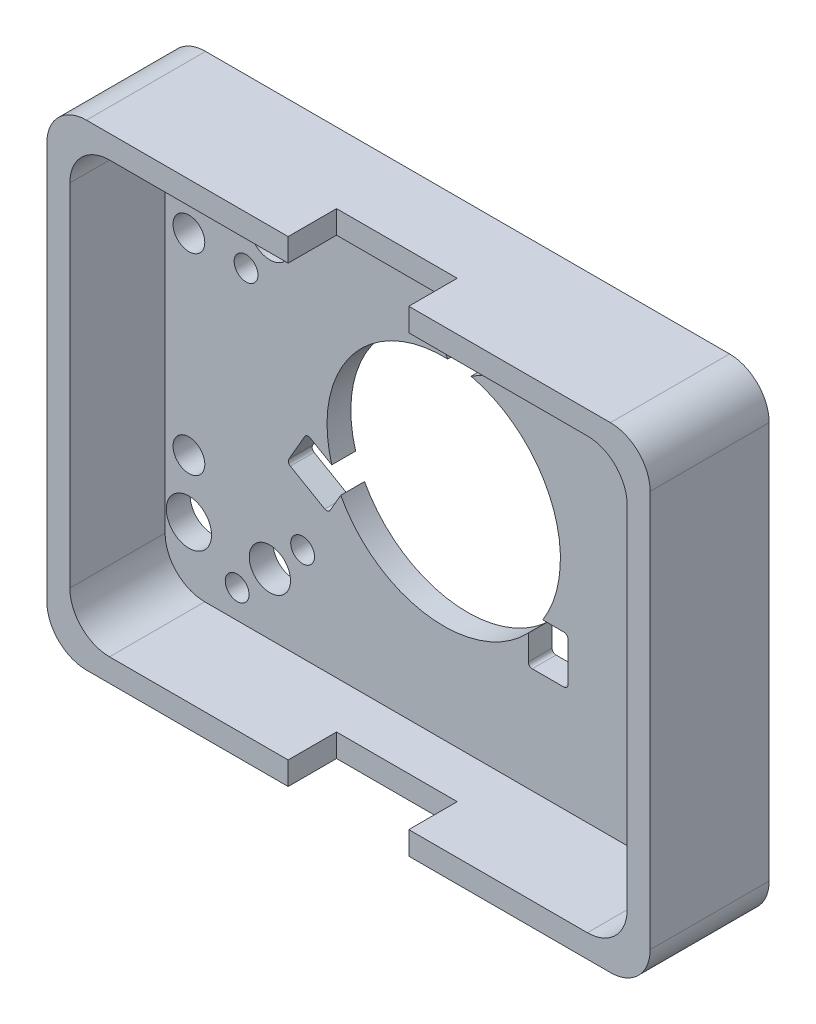
SolidWorks part; units mm, degrees
ref_plane "前基準面" through (0, 0, 0) normal (0, 0, 1) x (1, 0, 0)
ref_plane "上基準面" through (0, 0, 0) normal (0, 1, 0) x (1, 0, 0)
ref_plane "右基準面" through (0, 0, 0) normal (1, 0, 0) x (0, 0, -1)
sketch "草圖1" plane through (0, 0, 0) normal (0, 0, 1) x (1, 0, 0)
  line L1 (-33, 30) -> (33, 30)
  line L2 (-38, 25) -> (-38, -25)
  line L3 (-33, -30) -> (33, -30)
  line L4 (38, 25) -> (38, -25)
  line L5 (-38, 30) -> (38, -30) construction
  line L6 (-38, -30) -> (38, 30) construction
  arc A0 (-38, -25) -> (-33, -30) centre (-33, -25) ccw
  arc A1 (33, -30) -> (38, -25) centre (33, -25) ccw
  arc A2 (33, 30) -> (38, 25) centre (33, 25) cw
  arc A3 (-33, 30) -> (-38, 25) centre (-33, 25) ccw
  point P0 (0, 0)
  dimension "D3" = 5
  dimension "D1" = 76
  dimension "D2" = 60
extrude "填料-伸長1" add sketch "草圖1" along normal blind 15
sketch "草圖2" plane through (0, 0, 15) normal (0, 0, 1) x (1, 0, 0)
  line L0 (33, 30) -> (-33, 30) construction
  line L1 (-30.1, 27.1) -> (30.1, 27.1)
  line L2 (-35.1, 22.1) -> (-35.1, -22.1)
  line L3 (-30.1, -27.1) -> (30.1, -27.1)
  line L4 (35.1, 22.1) -> (35.1, -22.1)
  line L5 (-35.1, 27.1) -> (35.1, -27.1) construction
  line L6 (-35.1, -27.1) -> (35.1, 27.1) construction
  line L8 (-38, 25) -> (-38, -25) construction
  arc A0 (-35.1, -22.1) -> (-30.1, -27.1) centre (-30.1, -22.1) ccw
  arc A1 (30.1, -27.1) -> (35.1, -22.1) centre (30.1, -22.1) ccw
  arc A2 (30.1, 27.1) -> (35.1, 22.1) centre (30.1, 22.1) cw
  arc A3 (-30.1, 27.1) -> (-35.1, 22.1) centre (-30.1, 22.1) ccw
  point P0 (0, 0)
  dimension "D3" = 5
  dimension "D1" = 2.9
  dimension "D2" = 2.9
extrude "除料-伸長1" cut sketch "草圖2" against normal blind 12
sketch "草圖3" plane through (0, 0, 0) normal (0, 1, 0) x (1, 0, 0)
  line L0 (0, 11.6056) -> (0, -27.4941) construction
  line L1 (0, -3) -> (14.7, -3)
  line L2 (30.1, -3) -> (-30.1, -3) construction
  line L3 (14.7, -3) -> (14.7, -1.9)
  line L6 (0, -1.9) -> (0, -3)
  line L7 (14.7, -1.9) -> (14.7, 0)
  line L8 (33, 0) -> (-33, 0) construction
  line L9 (14.7, 0) -> (0, 0)
  line L10 (0, 0) -> (0, -1.9)
  dimension "D1" = 14.7
  dimension "D2" = 14.7
  dimension "D3" = 1.1
revolve "除料-旋轉1" cut sketch "草圖3" angle 360 about L0
ref_plane "平面1" through (0, 0, 15) normal (0, 0, 1) x (1, 0, 0)
sketch "草圖4" plane through (0, 0, 15) normal (0, 0, 1) x (1, 0, 0)
  line L0 (0, 32.9941) -> (0, -32.6269) construction
  line L1 (-42.1259, 0) -> (41.8506, 0) construction
  line L2 (7.6, 30) -> (-7.6, 30)
  line L3 (33, 30) -> (-33, 30) construction
  line L4 (-7.6, 30) -> (-7.6, 27.1)
  line L5 (30.1, 27.1) -> (-30.1, 27.1) construction
  line L6 (-7.6, 27.1) -> (7.6, 27.1)
  line L7 (30.1, 27.1) -> (-30.1, 27.1) construction
  line L8 (0, 27.1) -> (0, 30)
  line L9 (7.6, 30) -> (7.6, 27.1)
  line L10 (-7.6, -30) -> (-7.6, -27.1)
  line L11 (7.6, -30) -> (-7.6, -30)
  line L12 (7.6, -30) -> (7.6, -27.1)
  line L13 (-7.6, -27.1) -> (7.6, -27.1)
  dimension "D1" = 7.6
extrude "除料-伸長2" cut sketch "草圖4" against normal blind 6.1 contours L6 L9 L2 L4 | L11 L10 L13 L12
sketch "草圖5" plane through (0, 0, 3) normal (0, 0, 1) x (1, 0, 0)
  line L0 (0, 27.1) -> (0, -27.1) construction
  line L1 (30.1, 27.1) -> (-30.1, 27.1) construction
  line L2 (-7.6, -27.1) -> (7.6, -27.1) construction
  line L3 (-35.1, 0) -> (35.1, 0) construction
  line L4 (-35.1, 22.1) -> (-35.1, -22.1) construction
  line L5 (35.1, -22.1) -> (35.1, 22.1) construction
  line L6 (-35.1, 22.1) -> (-25.1, 22.1) construction
  line L7 (-25.1, 22.1) -> (-25.1, -22.1) construction
  line L8 (-25.1, -22.1) -> (-35.1, -22.1) construction
  line L9 (-35.1, 22.1) -> (-35.1, -22.1) construction
  line L10 (35.1, -22.1) -> (35.1, 22.1) construction
  line L11 (13.15, 0) -> (13.15, -16.56) construction
  line L12 (11.15, -8.28) -> (15.15, -8.28) construction
  line L13 (11.15, -7.78) -> (15.15, -7.78) construction
  line L14 (15.15, -7.78) -> (15.15, -8.78) construction
  line L15 (15.15, -8.78) -> (11.15, -8.78) construction
  line L16 (11.15, -8.78) -> (11.15, -7.78) construction
  line L17 (0, 0) -> (-14.4458, 25.0209) construction
  line L18 (-6.575, 11.3882) -> (6.9004, 19.1682) construction
  line L19 (-0.8373, 17.0103) -> (1.1627, 13.5462) construction
  line L20 (-0.8373, 17.0103) -> (0.0287, 17.5103) construction
  line L21 (0.0287, 17.5103) -> (2.0287, 14.0462) construction
  line L22 (2.0287, 14.0462) -> (1.1627, 13.5462) construction
  line L23 (-0.4043, 17.2603) -> (1.5957, 13.7962) construction
  line L24 (0, 0) -> (-14.6172, -25.3177) construction
  line L25 (-6.575, -11.3882) -> (-20.0504, -3.6082) construction
  line L30 (-12.3127, -5.7662) -> (-14.3127, -9.2303) construction
  line L31 (-12.3127, -5.7662) -> (-13.1787, -5.2662) construction
  line L32 (-13.1787, -5.2662) -> (-15.1787, -8.7303) construction
  line L33 (-15.1787, -8.7303) -> (-14.3127, -9.2303) construction
  line L34 (-12.7457, -5.5162) -> (-14.7457, -8.9803) construction
  line L35 (-17.5088, -2.7662) -> (-19.5088, -6.2303) construction
  line L36 (-19.5088, -6.2303) -> (-18.6428, -6.7303) construction
  line L37 (-16.6428, -3.2662) -> (-18.6428, -6.7303) construction
  line L38 (-16.6428, -3.2662) -> (-17.5088, -2.7662) construction
  line L39 (-17.0758, -3.0162) -> (-19.0758, -6.4803) construction
  line L40 (-19.3258, -6.9133) -> (-14.9957, -9.4133)
  line L41 (-16.8258, -2.5832) -> (-12.4957, -5.0832)
  line L42 (-17.5088, -2.7662) -> (-19.5088, -6.2303)
  line L43 (-12.3127, -5.7662) -> (-14.3127, -9.2303)
  line L44 (3.4928, 19.5103) -> (5.4928, 16.0462) construction
  line L45 (6.3588, 16.5462) -> (5.4928, 16.0462) construction
  line L46 (3.4928, 19.5103) -> (4.3588, 20.0103) construction
  line L47 (4.3588, 20.0103) -> (6.3588, 16.5462) construction
  line L48 (3.9258, 19.7603) -> (5.9258, 16.2962) construction
  line L49 (-0.6543, 17.6933) -> (3.6758, 20.1933)
  line L50 (6.1758, 15.8632) -> (1.8457, 13.3632)
  line L51 (4.3588, 20.0103) -> (6.3588, 16.5462)
  line L52 (-0.8373, 17.0103) -> (1.1627, 13.5462)
  line L53 (11.15, -13.78) -> (11.15, -12.78) construction
  line L54 (15.15, -13.78) -> (11.15, -13.78) construction
  line L55 (15.15, -12.78) -> (15.15, -13.78) construction
  line L56 (11.15, -12.78) -> (15.15, -12.78) construction
  line L57 (11.15, -13.28) -> (15.15, -13.28) construction
  line L58 (11.15, -7.78) -> (15.15, -7.78)
  line L59 (15.15, -13.78) -> (11.15, -13.78)
  line L60 (15.65, -8.28) -> (15.65, -13.28)
  line L61 (10.65, -8.28) -> (10.65, -13.28)
  circle A0 centre (-32.1, 19.4) radius 2.85
  circle A1 centre (32.1, 17.9) radius 2.85
  circle A2 centre (-32.1, -19.4) radius 2.85
  circle A3 centre (32.1, -19.4) radius 2.85
  circle A4 centre (11.15, -8.28) radius 0.5 construction
  circle A5 centre (15.15, -8.28) radius 0.5 construction
  circle A6 centre (-0.4043, 17.2603) radius 0.5 construction
  circle A7 centre (1.5957, 13.7962) radius 0.5 construction
  circle A8 centre (-12.7457, -5.5162) radius 0.5 construction
  circle A9 centre (-14.7457, -8.9803) radius 0.5 construction
  circle A10 centre (-19.0758, -6.4803) radius 0.5 construction
  circle A11 centre (-17.0758, -3.0162) radius 0.5 construction
  arc A12 (-16.8258, -2.5832) -> (-17.5088, -2.7662) centre (-17.0758, -3.0162) ccw
  arc A13 (-19.5088, -6.2303) -> (-19.3258, -6.9133) centre (-19.0758, -6.4803) ccw
  arc A14 (-14.9957, -9.4133) -> (-14.3127, -9.2303) centre (-14.7457, -8.9803) ccw
  arc A15 (-12.4957, -5.0832) -> (-12.3127, -5.7662) centre (-12.7457, -5.5162) cw
  circle A16 centre (3.9258, 19.7603) radius 0.5 construction
  circle A17 centre (5.9258, 16.2962) radius 0.5 construction
  arc A18 (-0.6543, 17.6933) -> (-0.8373, 17.0103) centre (-0.4043, 17.2603) ccw
  arc A19 (3.6758, 20.1933) -> (4.3588, 20.0103) centre (3.9258, 19.7603) cw
  arc A20 (6.3588, 16.5462) -> (6.1758, 15.8632) centre (5.9258, 16.2962) cw
  circle A21 centre (15.15, -13.28) radius 0.5 construction
  circle A22 centre (11.15, -13.28) radius 0.5 construction
  arc A23 (1.8457, 13.3632) -> (1.1627, 13.5462) centre (1.5957, 13.7962) cw
  arc A24 (11.15, -7.78) -> (10.65, -8.28) centre (11.15, -8.28) ccw
  arc A25 (10.65, -13.28) -> (11.15, -13.78) centre (11.15, -13.28) ccw
  arc A26 (15.15, -13.78) -> (15.65, -13.28) centre (15.15, -13.28) ccw
  arc A27 (15.65, -8.28) -> (15.15, -7.78) centre (15.15, -8.28) ccw
  circle A28 centre (-32.1, 12.1) radius 2
  circle A29 centre (32.1, 12.1) radius 2
  circle A30 centre (32.1, -12.1) radius 2
  circle A31 centre (-32.1, -12.1) radius 2
  point P35 (13.15, -8.28)
  point P38 (11.15, -8.28)
  point P50 (0.1627, 15.2782)
  point P62 (-13.3127, -7.4982)
  point P78 (-18.0758, -4.7482)
  point P96 (4.9258, 18.0282)
  point P106 (11.15, -13.28)
  point P112 (13.15, -13.28)
  circle M4 centre (0, 0) radius 14.7
  dimension "D2" = 5.7
  dimension "D6" = 5.7
  dimension "D8" = 13.15
  dimension "D25" = 5
  dimension "D31" = 4
  dimension "D1" = 10
  dimension "D3" = 2.7
  dimension "D4" = 3
  dimension "D5" = 4.2
  dimension "D7" = 3
  dimension "D9" = 4
  dimension "D10" = 1
  dimension "D11" = 7.78
  dimension "D12" = 120
  dimension "D13" = 13.15
  dimension "D14" = 4
  dimension "D15" = 1
  dimension "D16" = 7.78
  dimension "D17" = 120
  dimension "D18" = 13.15
  dimension "D19" = 4
  dimension "D20" = 1
  dimension "D21" = 7.78
  dimension "D22" = 5
  dimension "D23" = 4
  dimension "D24" = 1
  dimension "D26" = 1
  dimension "D27" = 4
  dimension "D28" = 5
  dimension "D29" = 4
  dimension "D30" = 1
  dimension "D32" = 15
extrude "除料-伸長3" cut sketch "草圖5" against normal through all contours L31 A8 | L31 A8 | L20 A6 | L20 A6 | L22 A7 | L22 A7 | A20 L51 A19 L49 A18 L52 L50 M4 | A23 L50 L52 M4 | L40 A14 L43 L41 A12 L42 A13 M4 | A30 | A0 | A2 | A3 | A1 | L61 A25 L59 A26 L60 A27 L58 A24 | L41 A15 L43 A14 L40 A13 L42 A12 | A28 | A31 | A29 region at (-16.1393, -6.0408, 3) region at (1.8089, 14.0824, 3) region at (2.8382, 16.9974, 3) region at (32.1, -12.1, 3)
sketch "草圖8" plane through (0, 0, 3) normal (0, 0, 1) x (1, 0, 0)
  line L0 (-30.1, -27.1) -> (30.1, -27.1) construction
  line L1 (30.1, 27.1) -> (-30.1, 27.1) construction
  line L2 (35.1, -22.1) -> (35.1, 22.1) construction
  line L3 (0, 27.1) -> (0, -27.1) construction
  line L4 (-7.6, 27.1) -> (7.6, 27.1) construction
  line L5 (-7.6, -27.1) -> (7.6, -27.1) construction
  circle A0 centre (-21.9, -19.4) radius 2.6
  circle A2 centre (21.9, 16.9) radius 2.6
  circle A3 centre (-21.9, 16.9) radius 2.6
  dimension "D2" = 5.2
  dimension "D3" = 10.2
  dimension "D5" = 5.2
  dimension "D1" = 7.7
  dimension "D4" = 13.2
extrude "除料-伸長4" cut sketch "草圖8" against normal through all
sketch "草圖9" plane through (0, 0, 0) normal (0, 0, -1) x (-1, 0, 0)
  line L0 (-21.9, 16.9) -> (21.9, 16.9) construction
  line L1 (21.9, 16.9) -> (21.9, -19.4) construction
  line L2 (0, 37.0703) -> (0, -36.0454) construction
  line L3 (17.7769, -15.2769) -> (26.0231, -23.5231) construction
  line L4 (-21.9, 23.8425) -> (-21.9, 16.9) construction
  circle A0 centre (-18.9, 21.9) radius 1.5
  circle A1 centre (-24.9, 11.9) radius 1.5
  circle A2 centre (24.9, 11.9) radius 1.5
  circle A3 centre (18.9, 21.9) radius 1.5
  circle A4 centre (17.7769, -15.2769) radius 1.5
  circle A5 centre (26.0231, -23.5231) radius 1.5
  dimension "D1" = 3
  dimension "D4" = 3
  dimension "D8" = 3
  dimension "D9" = 3
  dimension "D2" = 3
  dimension "D3" = 5
  dimension "D5" = 5
  dimension "D6" = 3
  dimension "D7" = 45
  dimension "D10" = 11.6619
extrude "除料-伸長5" cut sketch "草圖9" against normal up to next
